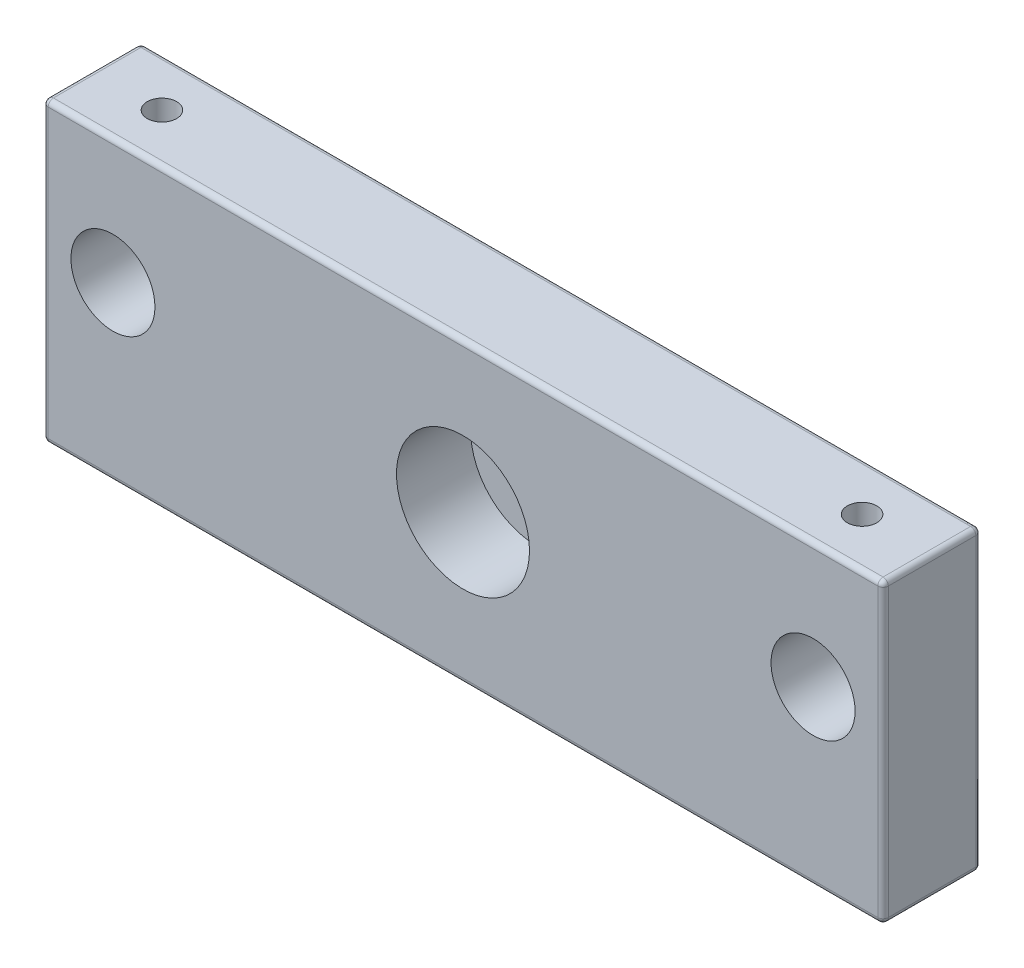
SolidWorks part; units mm, degrees
ref_plane "Front Plane" through (0, 0, 0) normal (0, 0, 1) x (1, 0, 0)
ref_plane "Top Plane" through (0, 0, 0) normal (0, 1, 0) x (1, 0, 0)
ref_plane "Right Plane" through (0, 0, 0) normal (1, 0, 0) x (0, 0, -1)
sketch "Sketch1" plane through (0, 0, 0) normal (0, 0, 1) x (1, 0, 0)
  line L1 (-60, -21.25) -> (60, -21.25)
  line L2 (-60, -21.25) -> (-60, 21.25)
  line L3 (-60, 21.25) -> (60, 21.25)
  line L4 (60, -21.25) -> (60, 21.25)
  line L5 (-60, -21.25) -> (60, 21.25) construction
  line L6 (-60, 21.25) -> (60, -21.25) construction
  point P0 (0, 0)
  dimension "D1" = 120
  dimension "D2" = 42.5
extrude "Boss-Extrude1" add sketch "Sketch1" along normal mid plane 14
sketch "Sketch2" plane through (0, 0, 7) normal (0, 0, 1) x (1, 0, 0)
  circle A0 centre (0, 0) radius 9.5
  dimension "D1" = 19
extrude "Cut-Extrude1" cut sketch "Sketch2" against normal blind 10.6
sketch "Sketch3" plane through (0, 0, -3.6) normal (0, 0, 1) x (1, 0, 0)
  circle A0 centre (0, 0) radius 5.5
  dimension "D1" = 11
extrude "Cut-Extrude2" cut sketch "Sketch3" against normal through all
sketch "Sketch5" plane through (0, 0, 7) normal (0, 0, 1) x (1, 0, 0)
  line L0 (-40.6477, 3.4) -> (36.4799, 3.4) construction
  circle A0 centre (-50, 3.4) radius 6
  circle A1 centre (50, 3.4) radius 6
  dimension "D1" = 12
  dimension "D2" = 12
  dimension "D4" = 50
  dimension "D3" = 50
  dimension "D5" = 3.4
extrude "Cut-Extrude4" cut sketch "Sketch5" against normal through all
sketch "Sketch6" plane through (0, -21.25, 0) normal (0, -1, 0) x (1, 0, 0)
  line L0 (-60, 0) -> (60, 0) construction
  line L1 (-60, 7) -> (-60, -7) construction
  line L2 (60, 7) -> (60, -7) construction
  circle A0 centre (-50, 0) radius 2.1
  circle A1 centre (-25, 0) radius 2.1
  circle A2 centre (25, 0) radius 2.1
  circle A3 centre (50, 0) radius 2.1
  circle A4 centre (-37.5, 0) radius 1.25
  circle A5 centre (37.5, 0) radius 1.25
  dimension "D1" = 4.2
  dimension "D2" = 4.2
  dimension "D3" = 4.2
  dimension "D4" = 4.2
  dimension "D5" = 10
  dimension "D9" = 2.5
  dimension "D10" = 2.5
  dimension "D11" = 22.5
  dimension "D12" = 22.5
  dimension "D6" = 35
  dimension "D7" = 10
  dimension "D8" = 35
extrude "Cut-Extrude5" cut sketch "Sketch6" against normal blind 10
fillet "Fillet1" radius 0.75 12 edges at (60, 21.25, 0) (60, 0, -7) (0, 21.25, -7) (60, 0, 7) (60, -21.25, 0) (0, -21.25, -7) (0, 21.25, 7) (-60, 21.25, 0) (-60, 0, -7) (0, -21.25, 7) (-60, -21.25, 0) (-60, 0, 7)
sketch "Sketch7" plane through (0, 21.25, 0) normal (0, 1, 0) x (1, 0, 0)
  line L0 (-1000, 0) -> (49000, 0) construction
  circle A0 centre (-50, 0) radius 2.1
  circle A1 centre (50, 0) radius 2.1
  dimension "D1" = 50
  dimension "D2" = 50
  dimension "D3" = 4.2
  dimension "D4" = 4.2
extrude "Cut-Extrude6" cut sketch "Sketch7" against normal up to next
